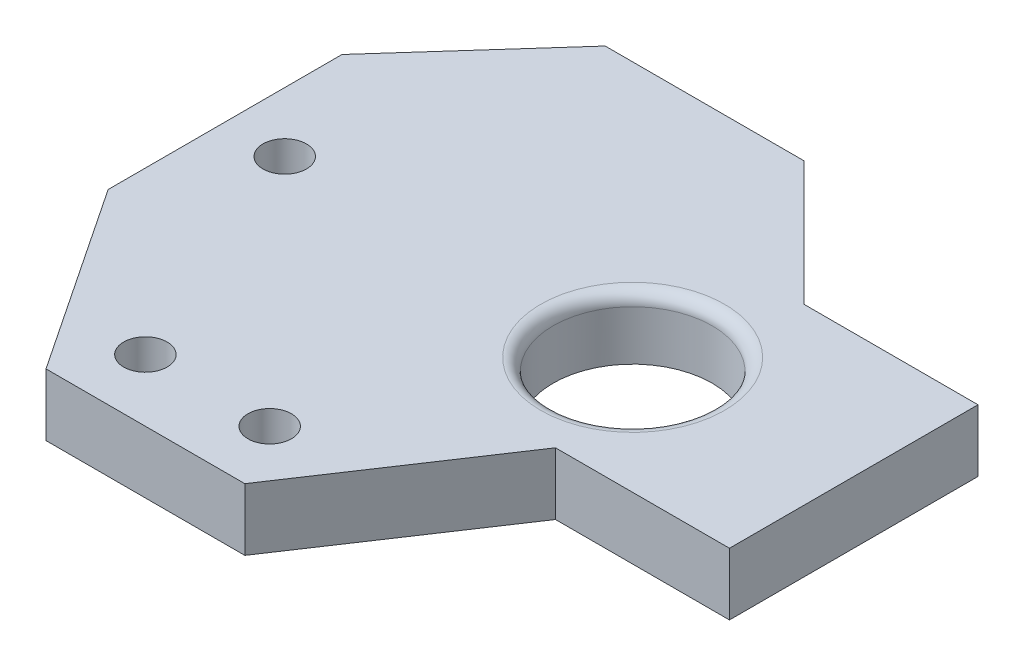
SolidWorks part; units mm, degrees
ref_plane "Front Plane" through (0, 0, 0) normal (0, 0, 1) x (1, 0, 0)
ref_plane "Top Plane" through (0, 0, 0) normal (0, 1, 0) x (1, 0, 0)
ref_plane "Right Plane" through (0, 0, 0) normal (1, 0, 0) x (0, 0, -1)
sketch "Sketch1" plane through (0, 0, 0) normal (0, 1, 0) x (1, 0, 0)
  line L0 (0, 33.8197) -> (10, 45)
  line L1 (0, 0) -> (50, 0)
  line L2 (0, 0) -> (0, 45)
  line L3 (0, 45) -> (50, 45)
  line L4 (50, 0) -> (50, 45)
  line L5 (0, 15) -> (10, 0)
  line L6 (26, 45) -> (36, 35)
  line L7 (26, 0) -> (36, 15)
  line L8 (36, 15) -> (50, 15)
  line L9 (36, 35) -> (50, 35)
  line L10 (50, 25) -> (0, 25) construction
  circle A1 centre (13, 5) radius 1.75
  circle A2 centre (23, 5) radius 1.75
  dimension "D15" = 10
  dimension "D16" = 3.5
  dimension "D24" = 3
  dimension "D25" = 3
  dimension "D17" = 3.5
  dimension "D1" = 45
  dimension "D2" = 50
  dimension "D3" = 15
  dimension "D4" = 10
  dimension "D5" = 10
  dimension "D6" = 15
  dimension "D7" = 16
  dimension "D8" = 16
  dimension "D9" = 10
  dimension "D10" = 10
  dimension "D11" = 10
  dimension "D12" = 20
  dimension "D13" = 10
  dimension "D18" = 5
extrude "Boss-Extrude1" add sketch "Sketch1" along normal blind 5 contours L4 L10 L2 L5 L1 L7 L8 | L10 L4 L9 L6 L3 L0 L2 | L10 | L10 region at (22.3613, 0, -23.5179)
ref_plane "Plane1" through (0, 0, 0) normal (0, -1, 0) x (-1, 0, 0)
sketch "Sketch2" plane through (0, 0, 0) normal (0, -1, 0) x (-1, 0, 0)
  line L0 (0, 24.4098) -> (-68.9029, 24.4098) construction
  line L1 (0, 15) -> (0, 33.8197) construction
  circle A0 centre (-4.8, 24.4098) radius 1.75
  circle A1 centre (-32.8, 24.4098) radius 6.4
  dimension "D1" = 4.8
  dimension "D2" = 12.8
  dimension "D3" = 28
extrude "Cut-Extrude1" cut sketch "Sketch2" against normal blind 10
fillet "Fillet1" radius 1 1 edges at (32.8, 5, -18.0098)
